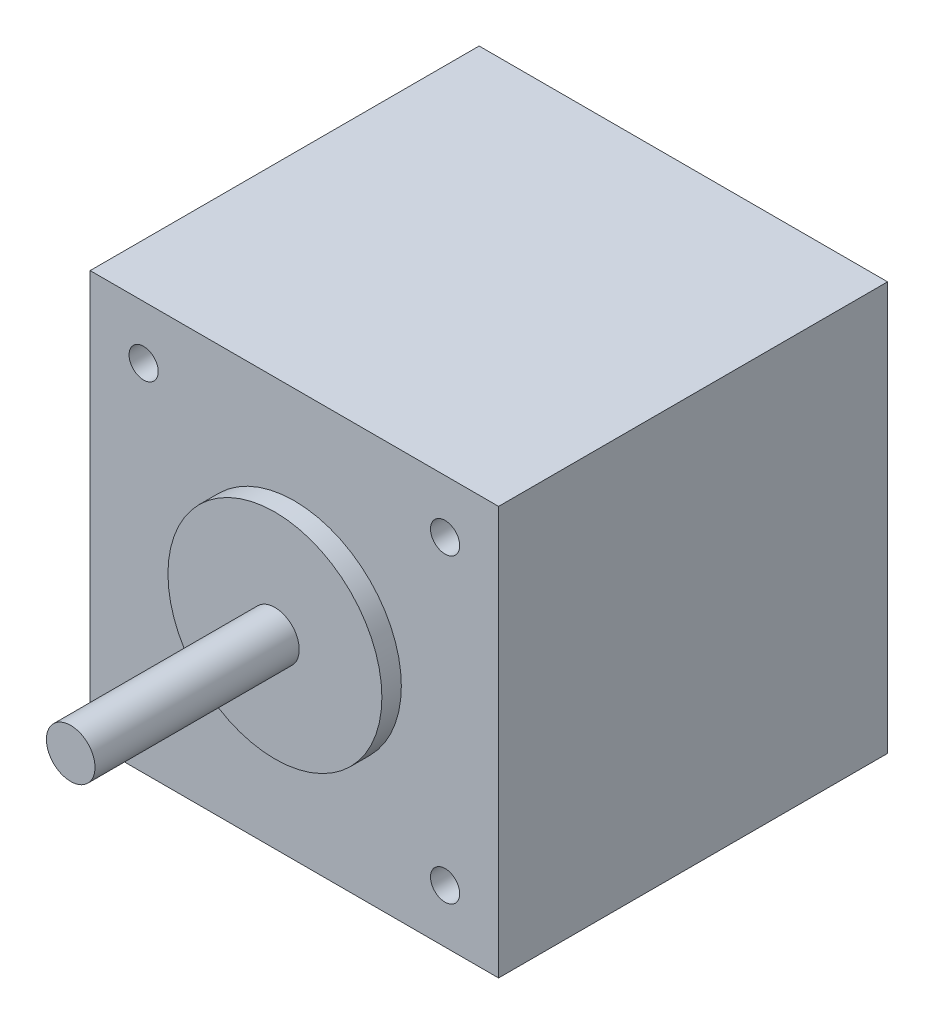
SolidWorks part; units mm, degrees
ref_plane "Спереди" through (0, 0, 0) normal (0, 0, 1) x (1, 0, 0)
ref_plane "Сверху" through (0, 0, 0) normal (0, 1, 0) x (1, 0, 0)
ref_plane "Справа" through (0, 0, 0) normal (1, 0, 0) x (0, 0, -1)
other "Configuration Table"
sketch "Эскиз1" plane through (0, 0, 0) normal (0, 0, 1) x (1, 0, 0)
  line L1 (-21, -21) -> (21, -21)
  line L2 (-21, -21) -> (-21, 21)
  line L3 (-21, 21) -> (21, 21)
  line L4 (21, -21) -> (21, 21)
  line L5 (-21, -21) -> (21, 21) construction
  line L6 (-21, 21) -> (21, -21) construction
  point P0 (0, 0)
  dimension "D1" = 42
  dimension "D2" = 42
extrude "Корпус" add sketch "Эскиз1" along normal blind 40
sketch "Эскиз2" plane through (0, 0, 0) normal (0, 0, 1) x (1, 0, 0)
  circle A0 centre (0, 0) radius 2.5
extrude "Вал_ПРЕДВ" add sketch "Эскиз2" along normal blind 63
sketch "Эскиз3" plane through (0, 0, 0) normal (0, 0, 1) x (1, 0, 0)
  circle A0 centre (0, 0) radius 11
  dimension "D1" = 22
extrude "Буртик_ПРЕДВ" add sketch "Эскиз3" along normal blind 42
sketch "Эскиз4" plane through (0, 0, 0) normal (0, 0, 1) x (1, 0, 0)
  circle A0 centre (-15.5, -15.5) radius 1.5
  circle A1 centre (-15.5, 15.5) radius 1.5
  circle A2 centre (15.5, -15.5) radius 1.5
  circle A3 centre (15.5, 15.5) radius 1.5
  dimension "D1" = 3
  dimension "D2" = 3
  dimension "D3" = 3
  dimension "D4" = 3
extrude "Крепеж_М3_ПРЕДВ" cut sketch "Эскиз4" against normal blind 4.5 from offset 40
equation "\"Мотор X ширина корпуса\"= 42.3"
equation "\"Мотор X высота корпуса\"= 42.3"
equation "\"Мотор X длина корпуса\"= 40"
equation "\"Мотор X вылет вала\"= 19.8"
equation "\"Мотор Y ширина корпуса\"= 42.3"
equation "\"Мотор Y высота корпуса\"= 42.3"
equation "\"Мотор Y длина корпуса\"= 48"
equation "\"Мотор Y вылет вала\"= 30"
equation "\"Мотор Z ширина корпуса\"= 42"
equation "\"Мотор Z высота корпуса\"= 42"
equation "\"Мотор Z длина корпуса\"= 40"
equation "\"Мотор Z вылет вала\"= 23"
equation "\"Мотор диаметр вала ПРЕДВ\"= 5"
equation "\"Мотор шаг крепления ПРЕДВ\"= 31"
equation "\"Мотор диаметр отверстий ПРЕДВ\"= 3"
equation "\"Мотор глубина отверстий ПРЕДВ\"= 4.5"
equation "\"Мотор диаметр буртика ПРЕДВ\"= 22"
equation "\"Мотор высота буртика ПРЕДВ\"= 2"
equation "\"Мотор диаметр шкива ПРЕДВ\"= 16"
equation "\"Мотор длина шкива ПРЕДВ\"= 12"
equation "\"Мотор отступ шкива ПРЕДВ\"= 5"
equation "\"Мотор X шаг градусов\"= 1.8"
equation "\"Мотор X ток А\"= 1.5"
equation "\"Мотор X сопротивление Ом\"= 1.3"
equation "\"Мотор X индуктивность мГн\"= 2"
equation "\"Мотор Y шаг градусов\"= 1.8"
equation "\"Мотор Y ток А\"= 2.2"
equation "\"Мотор Y сопротивление Ом\"= 0.9"
equation "\"Мотор Y индуктивность мГн\"= 2"
equation "\"Мотор Z шаг градусов\"= 1.8"
equation "\"Мотор Z ток А\"= 1"
equation "\"Мотор Z сопротивление Ом\"= 4"
equation "\"Мотор Z индуктивность мГн\"= 8"
equation "\"Мотор Y диаметр ротора\"= 25.78"
equation "\"D1@Эскиз1\" = \"Мотор Z ширина корпуса\""
equation "\"D2@Эскиз1\" = \"Мотор Z высота корпуса\""
equation "\"D1@Корпус\" = \"Мотор Z длина корпуса\""
equation "\"D1@Эскиз2\" = \"Мотор диаметр вала ПРЕДВ\""
equation "\"D1@Вал_ПРЕДВ\" = \"Мотор Z длина корпуса\" + \"Мотор Z вылет вала\""
equation "\"D1@Эскиз3\" = \"Мотор диаметр буртика ПРЕДВ\""
equation "\"D1@Буртик_ПРЕДВ\" = \"Мотор Z длина корпуса\" + \"Мотор высота буртика ПРЕДВ\""
equation "\"D1@Эскиз4\" = \"Мотор диаметр отверстий ПРЕДВ\""
equation "\"D2@Эскиз4\" = \"Мотор диаметр отверстий ПРЕДВ\""
equation "\"D3@Эскиз4\" = \"Мотор диаметр отверстий ПРЕДВ\""
equation "\"D4@Эскиз4\" = \"Мотор диаметр отверстий ПРЕДВ\""
equation "\"D1@Крепеж_М3_ПРЕДВ\" = \"Мотор глубина отверстий ПРЕДВ\""
equation "\"D19@Крепеж_М3_ПРЕДВ\" = \"Мотор Z длина корпуса\""
equation "\"Ширина груза\"= 420"
equation "\"Глубина груза\"= 490"
equation "\"Высота груза\"= 297"
equation "\"Ширина ячейки\"= \"Ширина груза\" + 10"
equation "\"Глубина ячейки\"= \"Глубина груза\" + 10"
equation "\"Высота ячейки\"= \"Высота груза\" + 10 + 13"
equation "\"Колво ячеек ширина\"= 2"
equation "\"Колво ячеек высота\"= 2"
equation "\"Толщина стенки\"= 10"
equation "\"Крепление дверцы\"= 5"
equation "\"Ширина рейки\"= \"Толщина шестерни\""
equation "\"Высота рейки\"= 20"
equation "\"Высота пола\"= 20"
equation "\"Колво полозьев\"= 5"
equation "\"Отступ рейки\"= 20"
equation "\"Глубина каретки\"= \"Глубина ячейки\" + 80"
equation "\"Отступ шпильки\"= 20"
equation "\"Диаметр шпильки\"= 5"
equation "\"Длинна шпильки\"= ( \"Высота ячейки\" + \"Толщина стенки\" + \"Высота пола\" ) * \"Колво ячеек высота\" + ( \"Толщина стенки\" + \"Отступ рейки\" ) * 2"
equation "\"Ширина пластины\"= 50  "
equation "\"Высота зона выгрузки\"= \"Высота ячейки\" * 2 + \"Толщина стенки\" * 2"
equation "\"Колво выгрузки\"= 1"
equation "\"Отступ крепления мотора фиксации\" = 30"
equation "\"Диаметр оси\"= 10"
equation "\"Диаметр ролика\"= 20"
equation "\"Колво роликов\"= 10"
equation "\"Шаг роликов\"= \"Диаметр ролика\" + 20"
equation "\"Ширина ячейки выгрузки\"= \"Ширина ячейки\" + \"Толщина стенки\" + \"Отступ крепления мотора фиксации\"*2"
equation "\"Длинна рейки\"= ( \"Ширина ячейки\" + \"Толщина стенки\" + \"Крепление дверцы\" ) * \"Колво ячеек ширина\" + \"Ширина ячейки выгрузки\" * \"Колво выгрузки\" + \"Толщина стенки\""
